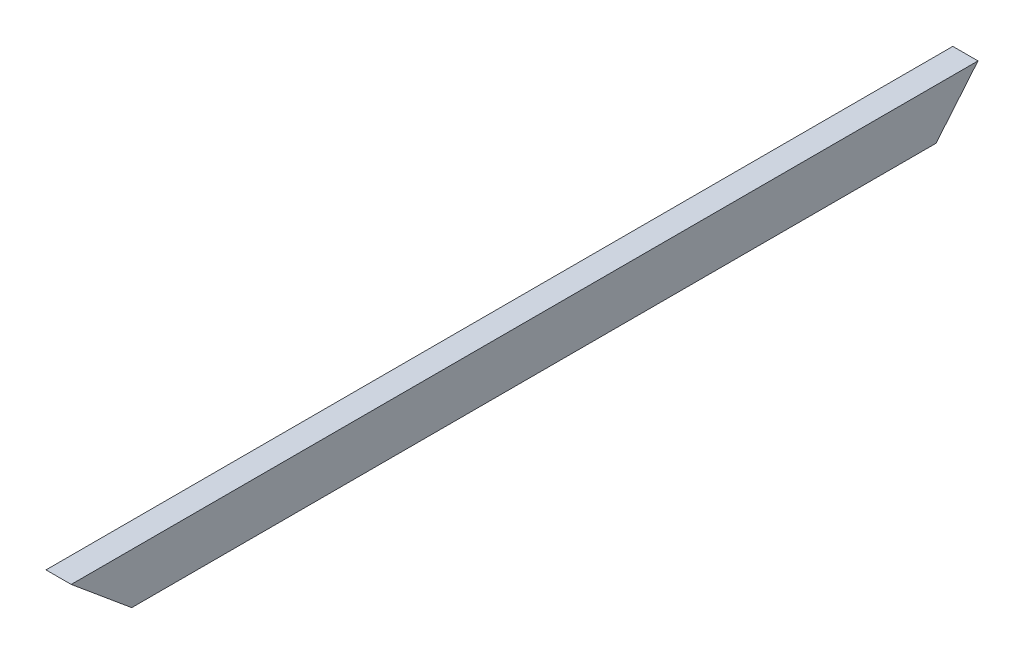
SolidWorks part; units mm, degrees
material "6063-T6"
ref_plane "Front" through (0, 0, 0) normal (0, 0, 1) x (1, 0, 0)
ref_plane "Top" through (0, 0, 0) normal (0, 1, 0) x (1, 0, 0)
ref_plane "Right" through (0, 0, 0) normal (1, 0, 0) x (0, 0, -1)
sketch "Sketch1" plane through (0, 0, 0) normal (0, 0, 1) x (1, 0, 0)
  line L0 (3.175, 3.175) -> (3.175, 22.225)
  line L1 (0, 0) -> (12.7, 0)
  line L2 (0, 0) -> (0, 25.4)
  line L3 (0, 25.4) -> (12.7, 25.4)
  line L4 (12.7, 0) -> (12.7, 25.4)
  line L5 (0, 0) -> (12.7, 25.4) construction
  line L6 (0, 25.4) -> (12.7, 0) construction
  line L7 (3.175, 22.225) -> (9.525, 22.225)
  line L8 (9.525, 3.175) -> (9.525, 22.225)
  line L9 (3.175, 3.175) -> (9.525, 3.175)
  point P4 (6.35, 12.7)
  dimension "D1" = 25.4
  dimension "D2" = 12.7
  dimension "D3" = 3.175
extrude "Boss-Extrude1" add sketch "Sketch1" along normal blind 457.2
sketch "Sketch2" plane through (12.7, 0, 0) normal (1, 0, 0) x (0, 0, -1)
  line L1 (-501.8856, 62.5833) -> (-189.4924, -197.3618) construction
  line L2 (-457.2, 25.4) -> (-426.6751, 0)
  line L3 (-457.2, 25.4) -> (-457.2, 0)
  line L4 (-457.2, 0) -> (-426.6751, 0)
  line L5 (-457.2, 0) -> (0, 0) construction
extrude "Cut-Extrude1" cut sketch "Sketch2" against normal through all
sketch "Sketch3" plane through (12.7, 0, 0) normal (1, 0, 0) x (0, 0, -1)
  line L0 (-191.1135, -204.2737) -> (28.2152, 59.308) construction
  line L1 (-21.1356, 0) -> (0, 25.4)
  line L2 (0, 25.4) -> (0, 0)
  line L3 (0, 0) -> (-21.1356, 0)
  line L4 (-426.6751, 0) -> (0, 0) construction
extrude "Cut-Extrude2" cut sketch "Sketch3" against normal through all
